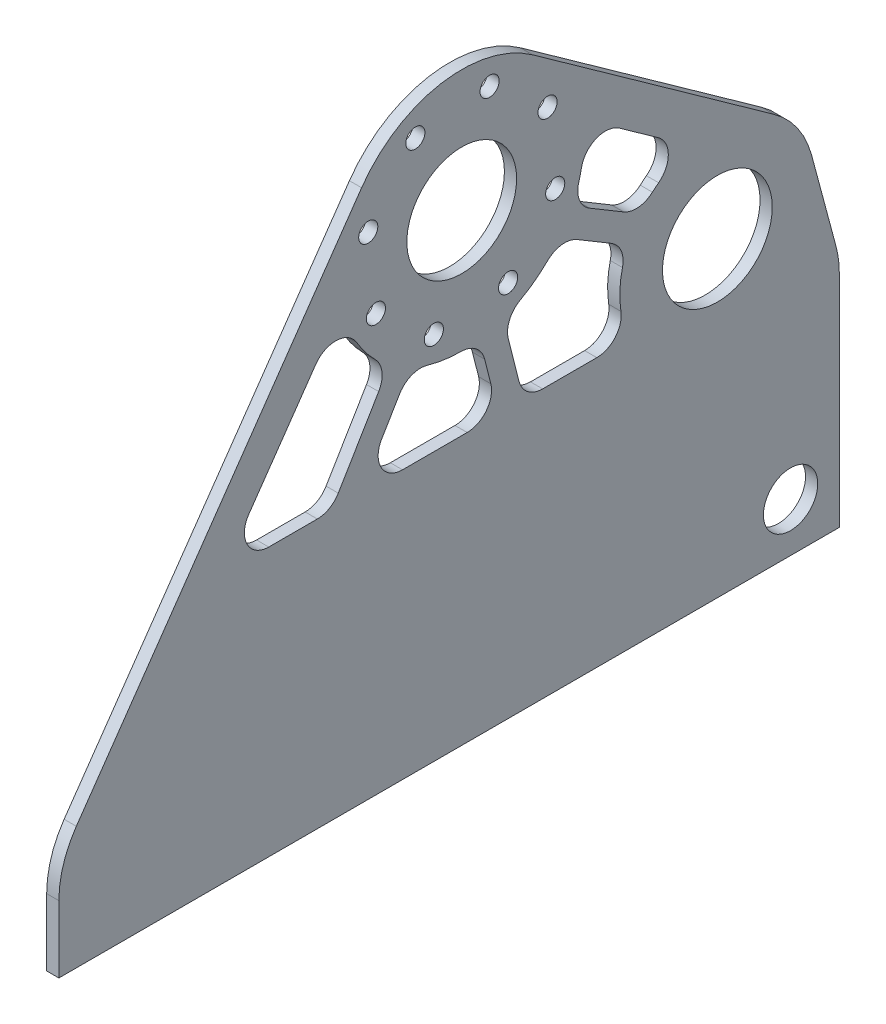
SolidWorks part; units mm, degrees
material "6061-T6 (SS)"
ref_plane "Front Plane" through (0, 0, 0) normal (0, 0, 1) x (1, 0, 0)
ref_plane "Top Plane" through (0, 0, 0) normal (0, 1, 0) x (1, 0, 0)
ref_plane "Right Plane" through (0, 0, 0) normal (1, 0, 0) x (0, 0, -1)
sketch "Sketch1" plane through (0, 0, 0) normal (1, 0, 0) x (0, 0, -1)
  line L0 (0, -25.4) -> (0, 31.864)
  line L13 (-203.2, -25.4) -> (0, -25.4)
  line L14 (-203.2, -25.4) -> (-203.2, -7.9618)
  line L15 (-198.6552, 6.5372) -> (-124.3806, 113.3737)
  line L16 (-203.2, 0) -> (0, 0) construction
  line L17 (-7.2155, 62.1365) -> (-0.8655, 38.438)
  line L18 (-79.8716, 121.0963) -> (-16.9981, 76.2396)
  circle A5 centre (-31.75, 55.5625) radius 14.2875
  circle A6 centre (-98.3115, 95.25) radius 14.2875 construction
  arc A7 (-79.8716, 121.0963) -> (-124.3806, 113.3737) centre (-98.3115, 95.25) ccw
  arc A8 (-16.9981, 76.2396) -> (-7.2155, 62.1365) centre (-31.75, 55.5625) cw
  circle A9 centre (-98.3115, 95.25) radius 14.2875
  arc A10 (-203.2, -7.9618) -> (-198.6552, 6.5372) centre (-177.8, -7.9618) cw
  arc A11 (-0.8655, 38.438) -> (0, 31.864) centre (-25.4, 31.864) cw
  point P4 (0, 0)
  dimension "D4" = 31.75
  dimension "D7" = 25.4
  dimension "D10" = 28.575
  dimension "D3" = 41.275
  dimension "D9" = 25.4
  dimension "D12" = 77.4954
  dimension "D13" = 63.5
  dimension "D14" = 63.5
  dimension "D5" = 25.4
  dimension "D8" = 28.575
  dimension "D2" = 15
  dimension "D6" = 203.2
extrude "Boss-Extrude1" add sketch "Sketch1" along normal blind 3.175
hole_wizard "#10 Clearance Hole1" positions "Sketch2" profile "Sketch3" hole size "#10" standard "ANSI Inch" end condition through all
sketch "Sketch2" plane through (3.175, 0, 0) normal (1, 0, 0) x (0, 0, -1)
  line L0 (-98.3115, 95.25) -> (-31.75, 55.5625) construction
  line L1 (-72.9115, 95.25) -> (-86.2351, 72.9046) construction
  circle A0 centre (-98.3115, 95.25) radius 25.4 construction
  circle A1 centre (-31.75, 55.5625) radius 14.2875 construction
  point P17 (-91.0503, 119.59)
  point P38 (-75.9661, 107.3265)
  point P39 (-73.9716, 87.9887)
  point P40 (-86.2351, 72.9046)
  point P41 (-105.5728, 70.91)
  point P42 (-120.657, 83.1735)
  point P43 (-122.6515, 102.5113)
  point P44 (-110.388, 117.5954)
  point P65 (0, 0)
  dimension "D1" = 50.8
  dimension "D2" = 8
sketch "Sketch3" plane through (3.175, 119.59, 91.0503) normal (0, 1, 0) x (0, 0, -1)
  line L0 (0, 0) -> (0, 3.175)
  line L1 (0, 3.175) -> (2.4892, 3.175)
  line L2 (2.4892, 3.175) -> (2.4892, 0)
  line L5 (2.4892, 0) -> (0, 0)
  line L11 (0, -6.35) -> (0, 107.95) construction
  dimension "Thru Hole Dia." = 4.9784
  dimension "Thru Hole Depth" = 3.175
sketch "Sketch9" plane through (3.175, 0, 0) normal (1, 0, 0) x (0, 0, -1)
  line L0 (0, 0) -> (-201.9199, 0) construction
  line L1 (0, -25.4) -> (0, 31.864) construction
  line L2 (0, -25.4) -> (0, 31.864) construction
  line L3 (-203.2, -25.4) -> (0, -25.4) construction
  line L4 (-160.6969, 44.45) -> (-129.5028, 89.3195)
  line L5 (-124.3806, 113.3737) -> (-198.6552, 6.5372) construction
  line L6 (-172.2976, 44.45) -> (-132.2977, 44.45) construction
  line L7 (-160.6969, 44.45) -> (-132.2977, 44.45)
  line L8 (-66.9456, 100.1737) -> (-38.6711, 80.0014)
  line L9 (-16.9981, 76.2396) -> (-79.8716, 121.0963) construction
  line L10 (-69.5519, 81.7985) -> (-51.7692, 71.1955)
  line L11 (-55.0212, 65.7415) -> (-72.8039, 76.3444)
  line L12 (-98.3115, 95.25) -> (-31.75, 55.5625) construction
  line L13 (-98.3115, 95.25) -> (-132.7027, 37.5711) construction
  line L14 (-98.3115, 95.25) -> (-81.8784, 30.2801) construction
  line L15 (-117.2171, 69.7423) -> (-132.2977, 44.45)
  line L16 (-124.9046, 44.45) -> (-111.763, 66.4903)
  line L17 (-93.6431, 63.8451) -> (-88.7375, 44.45)
  line L18 (-82.1875, 44.45) -> (-87.487, 65.4022)
  line L19 (-82.1875, 44.45) -> (0, 44.45) construction
  line L20 (-82.1875, 44.45) -> (-54.5901, 44.45)
  line L21 (-124.9046, 44.45) -> (-88.7375, 44.45) construction
  line L22 (-124.9046, 44.45) -> (-88.7375, 44.45)
  circle A0 centre (-12.7, -12.7) radius 7.0739
  arc A2 (-198.6552, 6.5372) -> (-203.2, -7.9618) centre (-177.8, -7.9618) ccw construction
  arc A3 (-69.5519, 81.7985) -> (-117.2171, 69.7423) centre (-98.3115, 95.25) ccw construction
  arc A4 (-79.8716, 121.0963) -> (-124.3806, 113.3737) centre (-98.3115, 95.25) ccw construction
  arc A5 (-55.0212, 65.7415) -> (-51.7692, 71.1955) centre (-31.75, 55.5625) ccw construction
  arc A6 (-7.2155, 62.1365) -> (-16.9981, 76.2396) centre (-31.75, 55.5625) ccw construction
  arc A7 (-129.5028, 89.3195) -> (-117.2171, 69.7423) centre (-98.3115, 95.25) ccw
  arc A8 (-54.5901, 44.45) -> (-55.0212, 65.7415) centre (-31.75, 55.5625) cw
  arc A9 (-51.7692, 71.1955) -> (-38.6711, 80.0014) centre (-31.75, 55.5625) cw
  arc A10 (-69.5519, 81.7985) -> (-66.9456, 100.1737) centre (-98.3115, 95.25) ccw
  arc A11 (-87.487, 65.4022) -> (-72.8039, 76.3444) centre (-98.3115, 95.25) ccw construction
  arc A12 (-87.487, 65.4022) -> (-72.8039, 76.3444) centre (-98.3115, 95.25) ccw
  arc A13 (-111.763, 66.4903) -> (-93.6431, 63.8451) centre (-98.3115, 95.25) ccw construction
  arc A14 (-111.763, 66.4903) -> (-93.6431, 63.8451) centre (-98.3115, 95.25) ccw
  dimension "D1" = 14.1478
  dimension "D3" = 12.7
  dimension "D2" = 12.7
  dimension "D4" = 9.525
  dimension "D5" = 44.45
  dimension "D6" = 9.525
  dimension "D7" = 6.35
  dimension "D8" = 6.35
  dimension "D9" = 6.35
  dimension "D10" = 45
  dimension "D11" = 45
extrude "Cut-Extrude1" cut sketch "Sketch9" against normal through all
fillet "Fillet1" radius 6.35 17 edges at (1.5875, 100.1737, 66.9456) (1.5875, 71.1955, 51.7692) (1.5875, 81.7985, 69.5519) (1.5875, 80.0014, 38.6711) (1.5875, 76.3444, 72.8039) (1.5875, 65.7415, 55.0212) (1.5875, 44.45, 82.1875) (1.5875, 65.4022, 87.487) (1.5875, 44.45, 54.5901) (1.5875, 44.45, 124.9046) (1.5875, 66.4903, 111.763) (1.5875, 63.8451, 93.6431) (1.5875, 44.45, 88.7375) (1.5875, 44.45, 160.6969) (1.5875, 89.3195, 129.5028) (1.5875, 69.7423, 117.2171) (1.5875, 44.45, 132.2977)
